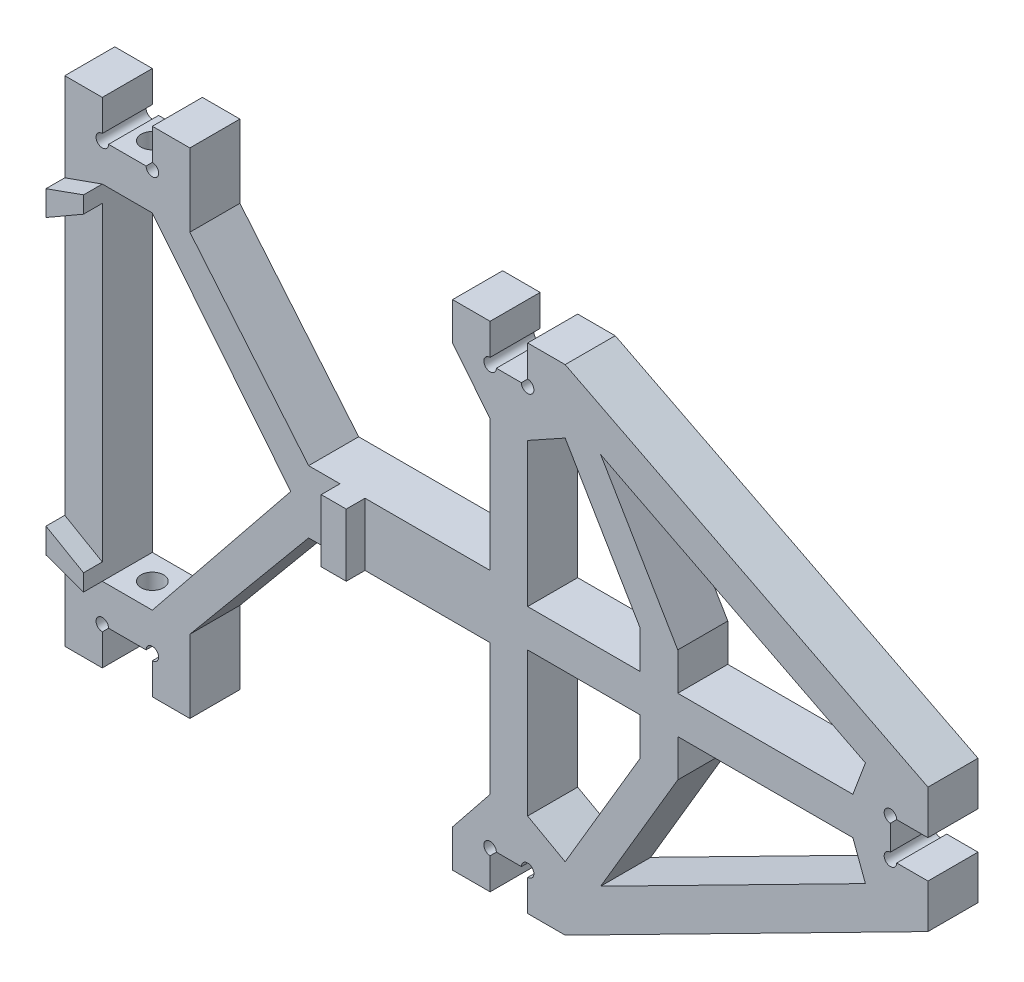
SolidWorks part; units mm, degrees
ref_plane "前视基准面" through (0, 0, 0) normal (0, 0, 1) x (1, 0, 0)
ref_plane "上视基准面" through (0, 0, 0) normal (0, 1, 0) x (1, 0, 0)
ref_plane "右视基准面" through (0, 0, 0) normal (1, 0, 0) x (0, 0, -1)
sketch "草图1" plane through (0, 0, 0) normal (0, 0, 1) x (1, 0, 0)
  line L12 (66, -1) -> (66, 1)
  line L13 (69, -5) -> (40, -19.75)
  line L14 (40, -19.75) -> (37, -19.75)
  line L15 (34.5, -16.75) -> (36.5, -16.75)
  line L16 (31, -16.75) -> (31, -19.75)
  line L17 (34, 13) -> (34, 2.5)
  line L18 (34, 13) -> (31, 16.75)
  line L19 (31, 19.75) -> (34, 19.75)
  line L20 (34, 19.75) -> (34, 17.25)
  line L21 (34.5, 16.75) -> (36.5, 16.75)
  line L22 (37, 13) -> (37, 1.5)
  line L23 (34, -19.75) -> (31, -19.75)
  line L24 (34, -13) -> (31, -16.75)
  line L25 (34, -19.75) -> (34, -17.25)
  line L26 (42.8383, -14.9406) -> (49, -4.5)
  line L27 (46, -1.5) -> (37, -1.5)
  line L28 (34, -2.5) -> (34, -13)
  line L29 (40, 14.6667) -> (46, 4.5)
  line L30 (46, 4.5) -> (46, 1.5)
  line L31 (63, 1.5) -> (64, 4.1774)
  line L32 (49, -1.5) -> (49, -4.5)
  line L33 (49, 4.5) -> (49, 1.5)
  line L34 (49, 1.5) -> (63, 1.5)
  line L35 (37, -17.25) -> (37, -19.75)
  line L36 (37, -1.5) -> (37, -13)
  line L37 (46, -1.5) -> (46, -4.5)
  line L38 (37, 19.75) -> (37, 17.25)
  line L39 (37, -13) -> (40, -14.6667)
  line L40 (46, -4.5) -> (40, -14.6667)
  line L41 (37, 13) -> (40, 14.6667)
  line L42 (37, 1.5) -> (46, 1.5)
  line L43 (42.8383, 14.9406) -> (64, 4.1774)
  line L44 (42.8383, -14.9406) -> (64, -4.1774)
  line L45 (49, 4.5) -> (42.8383, 14.9406)
  line L46 (66.5, 1.5) -> (69, 1.5)
  line L47 (69, 5) -> (69, 1.5)
  line L48 (63, -1.5) -> (49, -1.5)
  line L49 (37, 19.75) -> (40, 19.75)
  line L50 (40, 19.75) -> (69, 5)
  line L51 (31, 19.75) -> (31, 16.75)
  line L52 (69, -5) -> (69, -1.5)
  line L53 (66.5, -1.5) -> (69, -1.5)
  line L54 (63, -1.5) -> (64, -4.1774)
  line L55 (34, -2.5) -> (19.4926, -2.5)
  line L56 (34, 2.5) -> (19.4926, 2.5)
  line L57 (10, -13.9159) -> (19.4926, -2.5)
  line L58 (10, -19.75) -> (10, -13.9159)
  line L59 (10, -19.75) -> (7, -19.75)
  line L60 (7, -17.25) -> (7, -19.75)
  line L61 (3.5, -16.75) -> (6.5, -16.75)
  line L62 (3, -19.75) -> (3, -17.25)
  line L63 (3, -19.75) -> (0, -19.75)
  line L64 (3, -13.75) -> (7, -13.75)
  line L66 (18.0651, 0) -> (7, -13.75)
  line L67 (3, 13.75) -> (7, 13.75)
  line L68 (0, 19.75) -> (3, 19.75)
  line L69 (3, 19.75) -> (3, 17.25)
  line L70 (6.5, 16.75) -> (3.5, 16.75)
  line L71 (7, 19.75) -> (7, 17.25)
  line L72 (7, 19.75) -> (10, 19.75)
  line L73 (19.4926, 2.5) -> (10, 13.9159)
  line L74 (10, 19.75) -> (10, 13.9159)
  line L75 (7, 13.75) -> (18.0651, 0)
  line L78 (0, 19.75) -> (0, -19.75)
  line L81 (3, 13.75) -> (3, -13.75)
  arc A0 (66, -1) -> (66.5, -1.5) centre (66, -1.5) ccw
  arc A1 (37, -17.25) -> (36.5, -16.75) centre (37, -16.75) ccw
  arc A2 (34.5, -16.75) -> (34, -17.25) centre (34, -16.75) ccw
  arc A3 (34, 17.25) -> (34.5, 16.75) centre (34, 16.75) ccw
  arc A4 (36.5, 16.75) -> (37, 17.25) centre (37, 16.75) ccw
  arc A5 (66.5, 1.5) -> (66, 1) centre (66, 1.5) ccw
  arc A6 (7, -17.25) -> (6.5, -16.75) centre (7, -16.75) ccw
  arc A7 (3, 17.25) -> (3.5, 16.75) centre (3, 16.75) ccw
  arc A8 (6.5, 16.75) -> (7, 17.25) centre (7, 16.75) ccw
  arc A9 (3.5, -16.75) -> (3, -17.25) centre (3, -16.75) ccw
extrude "凸台-拉伸1" add sketch "草图1" along normal blind 4
sketch "草图2" plane through (0, -16.75, 0) normal (0, -1, 0) x (1, 0, 0)
  line L0 (3.5, 4) -> (6.5, 4) construction
  line L1 (3, 4) -> (3, 0) construction
  line L2 (7, 4) -> (7, 0) construction
  circle A0 centre (5, 2) radius 0.9
  dimension "D1" = 1.8
  dimension "D2" = 2
  dimension "D3" = 2
  dimension "D4" = 2
extrude "切除-拉伸1" cut sketch "草图2" against normal blind 52
sketch "草图3" plane through (0, 0, 4) normal (0, 0, 1) x (1, 0, 0)
  line L0 (3, 12.413) -> (3, 13.75)
  line L1 (3, 12.413) -> (0, 10.681)
  line L2 (0, 12.681) -> (0, 10.681)
  line L3 (0, 12.681) -> (3, 13.75)
  line L4 (24, -2.5) -> (24, 2.5)
  line L5 (24, -2.5) -> (22, -2.5)
  line L6 (22, 2.5) -> (22, -2.5)
  line L7 (22, 2.5) -> (24, 2.5)
  line L8 (3, -13.75) -> (3, -12.413)
  line L9 (3, -13.75) -> (0, -12.681)
  line L10 (0, -10.681) -> (0, -12.681)
  line L11 (0, -10.681) -> (3, -12.413)
extrude "凸台-拉伸2" add sketch "草图3" along normal blind 1.5
